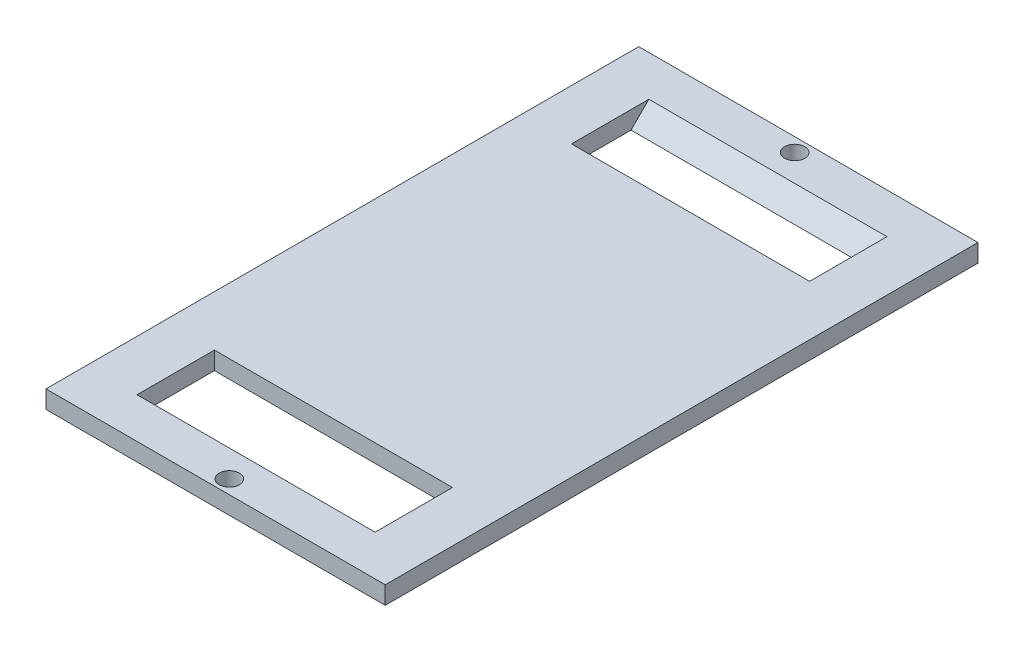
SolidWorks part; units mm, degrees
ref_plane "前视基准面" through (0, 0, 0) normal (0, 0, 1) x (1, 0, 0)
ref_plane "上视基准面" through (0, 0, 0) normal (0, 1, 0) x (1, 0, 0)
ref_plane "右视基准面" through (0, 0, 0) normal (1, 0, 0) x (0, 0, -1)
sketch "草图1" plane through (0, 0, 0) normal (0, 1, 0) x (1, 0, 0)
  line L1 (-28.5, 49.8) -> (28.5, 49.8)
  line L2 (-28.5, 49.8) -> (-28.5, -49.8)
  line L3 (-28.5, -49.8) -> (28.5, -49.8)
  line L4 (28.5, 49.8) -> (28.5, -49.8)
  line L5 (-28.5, 49.8) -> (28.5, -49.8) construction
  line L6 (-28.5, -49.8) -> (28.5, 49.8) construction
  circle A0 centre (0, 47.5) radius 1.7
  circle A1 centre (0, -47.5) radius 1.7
  point P0 (0, 0)
  dimension "D3" = 47.5
  dimension "D4" = 47.5
  dimension "D5" = 3.4
  dimension "D6" = 3.4
  dimension "D1" = 57
  dimension "D2" = 99.6
extrude "凸台-拉伸1" add sketch "草图1" along normal blind 3
sketch "草图2" plane through (0, 3, 0) normal (0, 1, 0) x (1, 0, 0)
  line L0 (0, 52.6523) -> (0, -54.7405) construction
  line L2 (-20, 40) -> (20, 40)
  line L3 (-20, 40) -> (-20, 30)
  line L4 (-20, 30) -> (20, 30)
  line L5 (20, 40) -> (20, 30)
  line L6 (-20, 40) -> (20, 30) construction
  line L7 (-20, 30) -> (20, 40) construction
  line L8 (-20, -30) -> (20, -30)
  line L9 (-20, -30) -> (-20, -40)
  line L10 (-20, -40) -> (20, -40)
  line L11 (20, -30) -> (20, -40)
  line L12 (-20, -30) -> (20, -40) construction
  line L13 (-20, -40) -> (20, -30) construction
  point P3 (0, 35)
  point P8 (0, -35)
  dimension "D1" = 40
  dimension "D2" = 40
  dimension "D3" = 10
  dimension "D4" = 10
  dimension "D5" = 40
  dimension "D6" = 40
extrude "切除-拉伸1" cut sketch "草图2" against normal blind 3
chamfer "倒角1" distance 3 angle 45 2 edges at (0, 3, 40) (0, 3, -40)
